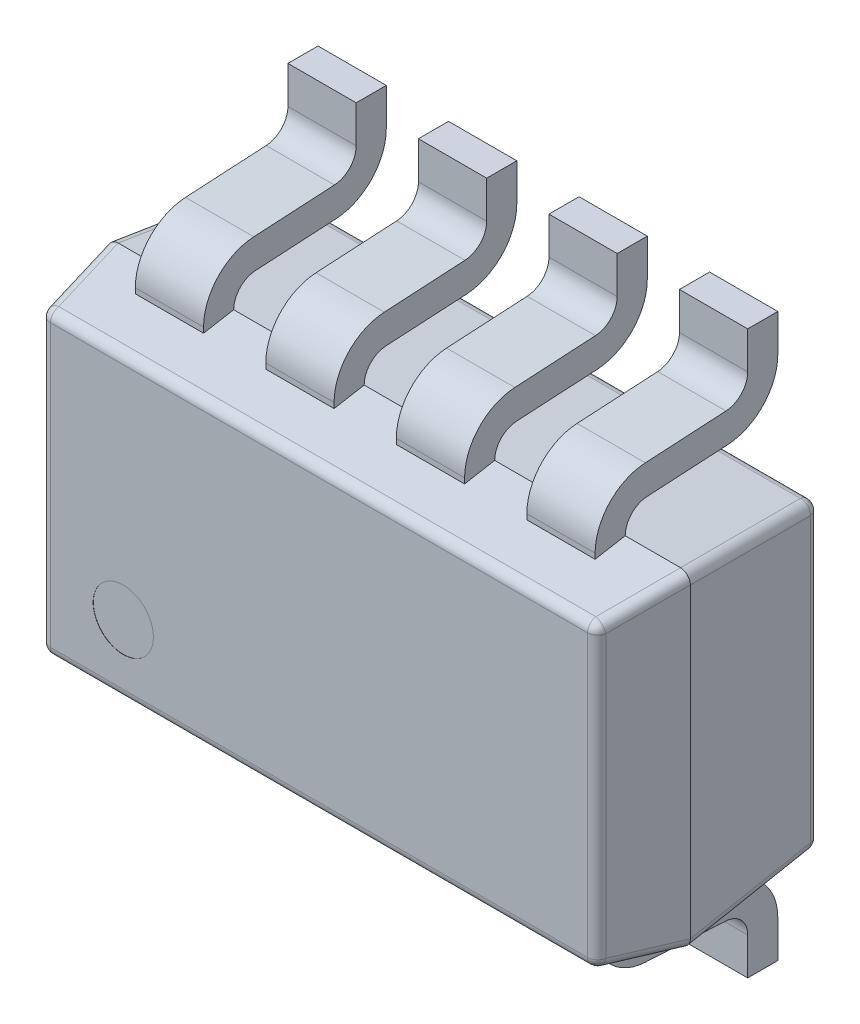
SolidWorks part; units mm, degrees
ref_plane "Спереди" through (0, 0, 0) normal (0, 0, 1) x (1, 0, 0)
ref_plane "Сверху" through (0, 0, 0) normal (0, 1, 0) x (1, 0, 0)
ref_plane "Справа" through (0, 0, 0) normal (1, 0, 0) x (0, 0, -1)
sketch "Эскиз1" plane through (0, 0, 0) normal (0, 0, 1) x (1, 0, 0)
  line L1 (-1.45, 0.8125) -> (1.45, 0.8125)
  line L2 (-1.45, 0.8125) -> (-1.45, -0.8125)
  line L3 (-1.45, -0.8125) -> (1.45, -0.8125)
  line L4 (1.45, 0.8125) -> (1.45, -0.8125)
  point P0 (0, 0)
  point P6 (1.45, 0)
  point P7 (0, 0.8125)
  dimension "D1" = 1.625
  dimension "D2" = 2.9
extrude "body" add sketch "Эскиз1" along normal blind 0.4 draft 10 and the other way blind 0.7 draft 5 from offset 0.76
sketch "Эскиз2" plane through (0, 0, 0) normal (1, 0, 0) x (0, 0, -1)
  line L0 (0, -1.4) -> (0, -1.2145)
  line L1 (0, -1.4) -> (-0.15, -1.4)
  line L2 (-0.76, -0.7513) -> (-0.76, -0.8125)
  line L3 (-0.91, 0.8125) -> (-0.91, 0.7513)
  line L4 (-0.25, -0.95) -> (-0.6515, -0.9273)
  line L5 (-0.15, -1.4) -> (-0.15, -1.2145)
  line L6 (-0.76, -0.7513) -> (-0.91, -0.7513)
  line L7 (-0.2585, -1.0998) -> (-0.66, -1.077)
  line L8 (-0.91, -0.8125) -> (-0.91, -0.7513)
  line L9 (-0.036, 0) -> (-1.0524, 0) construction
  line L10 (-0.2585, 1.0998) -> (-0.66, 1.077)
  line L11 (-0.76, 0.7513) -> (-0.91, 0.7513)
  line L12 (-0.15, 1.4) -> (-0.15, 1.2145)
  line L13 (-0.25, 0.95) -> (-0.6515, 0.9273)
  line L14 (-0.76, 0.7513) -> (-0.76, 0.8125)
  line L15 (0, 1.4) -> (-0.15, 1.4)
  line L16 (0, 1.4) -> (0, 1.2145)
  line L17 (-0.76, -0.8125) -> (-0.76, 0.8125) construction
  arc A0 (0, -1.2145) -> (-0.25, -0.95) centre (-0.265, -1.2145) ccw
  arc A1 (-0.15, -1.2145) -> (-0.2585, -1.0998) centre (-0.265, -1.2145) ccw
  arc A2 (-0.76, -0.8125) -> (-0.6515, -0.9273) centre (-0.645, -0.8125) ccw
  arc A3 (-0.66, -1.077) -> (-0.91, -0.8125) centre (-0.645, -0.8125) cw
  arc A4 (-0.66, 1.077) -> (-0.91, 0.8125) centre (-0.645, 0.8125) ccw
  arc A5 (-0.76, 0.8125) -> (-0.6515, 0.9273) centre (-0.645, 0.8125) cw
  arc A6 (-0.15, 1.2145) -> (-0.2585, 1.0998) centre (-0.265, 1.2145) cw
  arc A7 (0, 1.2145) -> (-0.25, 0.95) centre (-0.265, 1.2145) cw
  point P34 (-0.6, -0.7243)
  point P37 (0, 0)
  point P38 (0, 0)
  point P39 (0, 0)
  point P40 (-0.6, -0.8125)
  point P42 (-0.5169, -1.0721)
  dimension "D1" = 2.8
  dimension "D2" = 0.15
  dimension "D3" = 0.45
  dimension "D4" = 0.25
extrude "pins4-5" add sketch "Эскиз2" along normal blind 0.17 and the other way blind 0.17 from offset 0.955
sketch "Эскиз3" plane through (0, 0, 1.16) normal (0, 0, 1) x (1, 0, 0)
  circle A0 centre (-0.975, -0.4) radius 0.15
  dimension "D1" = 0.975
  dimension "D3" = 0.3
  dimension "D2" = 0.4
extrude "mark" cut sketch "Эскиз3" against normal blind 0.001
fillet "conges" radius 0.05 16 edges at (-1.3888, 0, 0.06) (0, -0.7513, 0.06) (1.4147, -0.7772, 0.96) (1.4147, 0.7772, 0.96) (-1.4147, 0.7772, 0.96) (-1.4147, -0.7772, 0.96) (1.3795, 0, 1.16) (0, 0.742, 1.16) (-1.3795, 0, 1.16) (0, -0.742, 1.16) (1.3888, 0, 0.06) (0, 0.7513, 0.06) (1.4194, -0.7819, 0.41) (-1.4194, -0.7819, 0.41) (-1.4194, 0.7819, 0.41) (1.4194, 0.7819, 0.41)
pattern_linear "repetition pins" count 4 spacing 0.65 along (-1, 0, 0) of "pins4-5"
